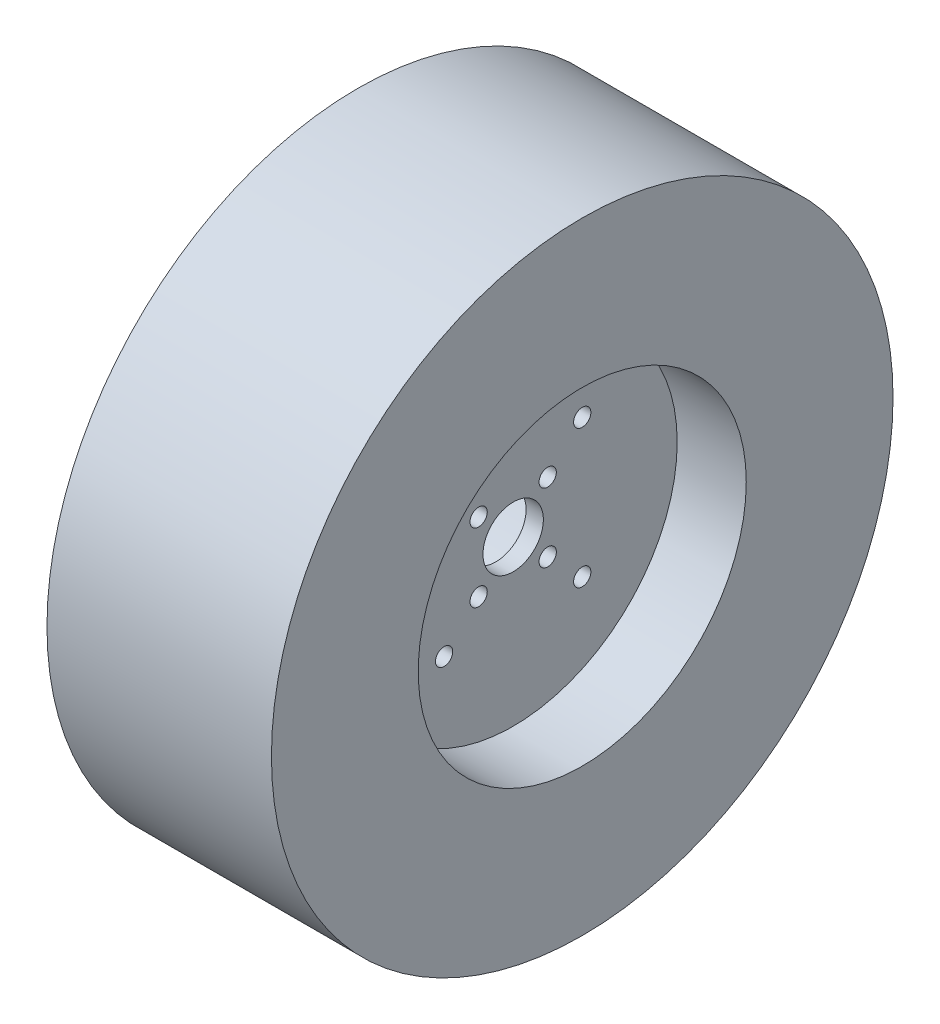
SolidWorks part; units mm, degrees
ref_plane "Front Plane" through (0, 0, 0) normal (0, 0, 1) x (1, 0, 0)
ref_plane "Top Plane" through (0, 0, 0) normal (0, 1, 0) x (1, 0, 0)
ref_plane "Right Plane" through (0, 0, 0) normal (1, 0, 0) x (0, 0, -1)
ref_plane "PL_Ym32" through (-32, 0, 0) normal (1, 0, 0) x (0, 0, -1)
sketch "SK_Tyre" plane through (-32, 0, 0) normal (1, 0, 0) x (0, 0, -1)
  circle A0 centre (0, 0) radius 72
  dimension "D1" = 144
extrude "EX_Tyre" add sketch "SK_Tyre" along normal blind 52
sketch "SK_RecessDeep" plane through (-32, 0, 0) normal (1, 0, 0) x (0, 0, -1)
  circle A0 centre (0, 0) radius 38
  dimension "D1" = 76
extrude "CUT_RecessDeep" cut sketch "SK_RecessDeep" along normal blind 32
ref_plane "PL_Yp20" through (20, 0, 0) normal (1, 0, 0) x (0, 0, -1)
sketch "SK_RecessShallow" plane through (20, 0, 0) normal (1, 0, 0) x (0, 0, -1)
  circle A0 centre (0, 0) radius 38
  dimension "D1" = 76
extrude "CUT_RecessShallow" cut sketch "SK_RecessShallow" against normal blind 16
sketch "SK_WebHoles" plane through (0, 0, 0) normal (1, 0, 0) x (0, 0, -1)
  circle A0 centre (0, 0) radius 7
  circle A1 centre (-8, 8) radius 2
  circle A2 centre (-8, -8) radius 2
  circle A3 centre (8, 8) radius 2
  circle A4 centre (8, -8) radius 2
  circle A5 centre (-16, 16) radius 2
  circle A6 centre (-16, -16) radius 2
  circle A7 centre (16, 16) radius 2
  circle A8 centre (16, -16) radius 2
  dimension "D1" = 14
  dimension "D4" = 4
  dimension "D7" = 4
  dimension "D10" = 4
  dimension "D13" = 4
  dimension "D16" = 4
  dimension "D19" = 4
  dimension "D22" = 4
  dimension "D25" = 4
  dimension "D2" = 8
  dimension "D3" = 8
  dimension "D5" = 8
  dimension "D6" = 8
  dimension "D8" = 8
  dimension "D9" = 8
  dimension "D11" = 8
  dimension "D12" = 8
  dimension "D14" = 16
  dimension "D15" = 16
  dimension "D17" = 16
  dimension "D18" = 16
  dimension "D20" = 16
  dimension "D21" = 16
  dimension "D23" = 16
  dimension "D24" = 16
extrude "CUT_WebHoles" cut sketch "SK_WebHoles" along normal blind 4
ref_axis "AX_X" through (0, 0, -79.2) along (0, 0, 1)
ref_axis "AX_Y" through (22.6, 0, 0) along (-1, 0, 0)
ref_axis "AX_Z" through (0, 79.2, 0) along (0, -1, 0)
sketch "SK_F_IF_Center" plane through (0, 0, 0) normal (0, 1, 0) x (1, 0, 0)
  point P0 (-6, 0)
  dimension "D1" = 6
